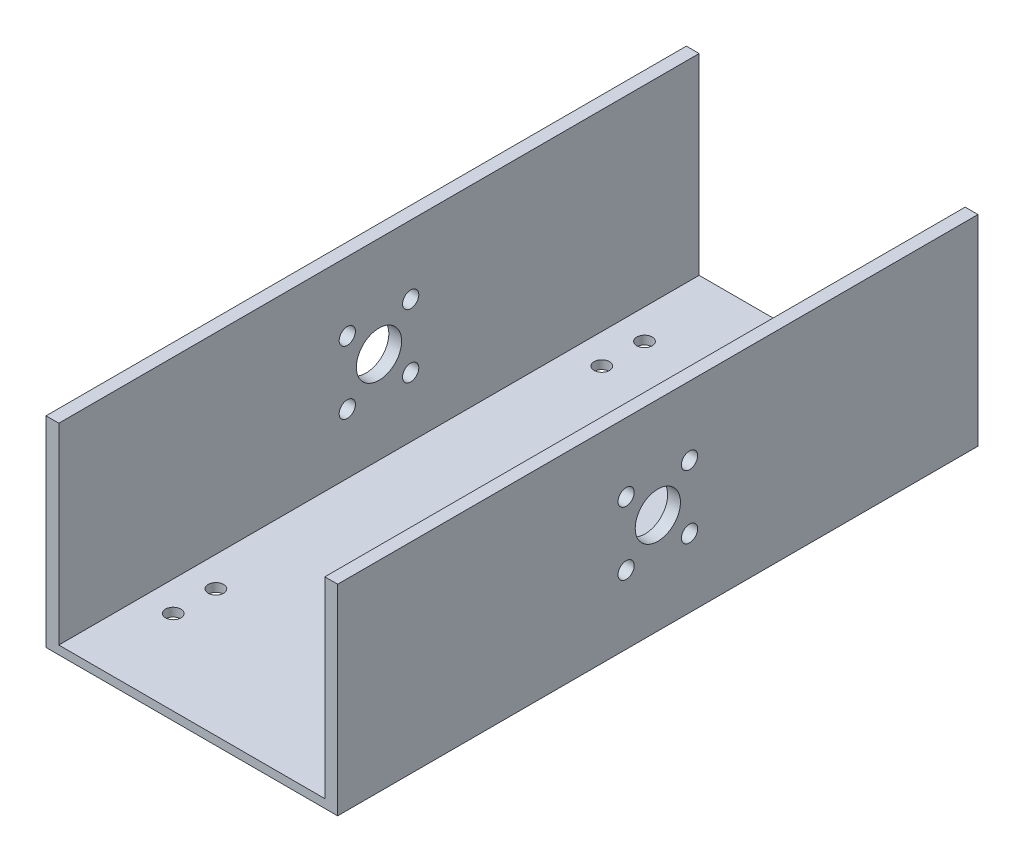
SolidWorks part; units mm, degrees
ref_plane "Alzado" through (0, 0, 0) normal (0, 0, 1) x (1, 0, 0)
ref_plane "Planta" through (0, 0, 0) normal (0, 1, 0) x (1, 0, 0)
ref_plane "Vista lateral" through (0, 0, 0) normal (1, 0, 0) x (0, 0, -1)
sketch "Croquis1" plane through (0, 0, 0) normal (0, 1, 0) x (1, 0, 0)
  line L0 (34.16, 45.2) -> (-34.16, 45.2) construction
  line L1 (34.16, 75) -> (-34.16, 75)
  line L2 (34.16, 75) -> (34.16, -75)
  line L3 (34.16, -75) -> (-34.16, -75)
  line L4 (-34.16, 75) -> (-34.16, -75)
  line L5 (34.16, 75) -> (-34.16, -75) construction
  line L6 (34.16, -75) -> (-34.16, 75) construction
  line L7 (34.16, 0) -> (-34.16, 0) construction
  line L8 (34.16, 55.2) -> (-34.16, 55.2) construction
  line L9 (24.16, 45.2) -> (24.16, 55.2) construction
  line L10 (-24.16, 45.2) -> (-24.16, 55.2) construction
  circle A0 centre (24.16, 45.2) radius 1.8
  circle A1 centre (24.16, 55.2) radius 1.8
  circle A2 centre (-24.16, -55.2) radius 1.8
  circle A3 centre (24.16, -55.2) radius 1.8
  circle A4 centre (-24.16, 45.2) radius 1.8
  circle A5 centre (-24.16, 55.2) radius 1.8
  circle A6 centre (-24.16, -45.2) radius 1.8
  circle A7 centre (24.16, -45.2) radius 1.8
  point P0 (0, 0)
  point P1 (0, 0)
  dimension "D3" = 48.32
  dimension "D4" = 3.6
  dimension "D5" = 19.8
  dimension "D1" = 150
  dimension "D2" = 10
  dimension "D6" = 10
  dimension "D7" = 10
extrude "Saliente-Extruir1" add sketch "Croquis1" along normal blind 2
sketch "Croquis2" plane through (0, 2, 0) normal (0, 1, 0) x (1, 0, 0)
  line L0 (-34.16, -75) -> (34.16, -75) construction
  line L1 (-34.16, 75) -> (-31.16, 75)
  line L2 (-34.16, 75) -> (-34.16, -75)
  line L3 (-34.16, -75) -> (-31.16, -75)
  line L4 (-31.16, 75) -> (-31.16, -75)
  dimension "D1" = 3
extrude "Saliente-Extruir2" add sketch "Croquis2" along normal blind 45
sketch "Croquis3" plane through (0, 2, 0) normal (0, 1, 0) x (1, 0, 0)
  line L0 (-31.16, -75) -> (34.16, -75) construction
  line L1 (34.16, 75) -> (31.16, 75)
  line L2 (34.16, 75) -> (34.16, -75)
  line L3 (34.16, -75) -> (31.16, -75)
  line L4 (31.16, 75) -> (31.16, -75)
  dimension "D1" = 3
extrude "Saliente-Extruir3" add sketch "Croquis3" along normal up to surface (45 mm away) up to face at (-32.66, 47, 0)
sketch "Croquis4" plane through (-34.16, 0, 0) normal (-1, 0, 0) x (0, 0, 1)
  line L0 (0, 47) -> (0, 0) construction
  line L1 (-75, 47) -> (75, 47) construction
  line L2 (-75, 0) -> (75, 0) construction
  line L3 (-75, 23.5) -> (75, 23.5) construction
  line L4 (-75, 47) -> (-75, 0) construction
  line L5 (75, 47) -> (75, 0) construction
  line L6 (7.4246, 30.9246) -> (0, 23.5) construction
  circle A0 centre (0, 23.5) radius 5.3
  circle A1 centre (0, 23.5) radius 10.5 construction
  circle A2 centre (7.4246, 30.9246) radius 1.9
  dimension "D1" = 3.8
  dimension "D2" = 21
  dimension "D3" = 10.6
  dimension "D4" = 45
extrude "Cortar-Extruir1" cut sketch "Croquis4" against normal through all
pattern_circular "MatrizC1" count 4 over 360 about axis through (-34.16, 23.5, 0) along (-1, 0, 0) of "Cortar-Extruir1"
